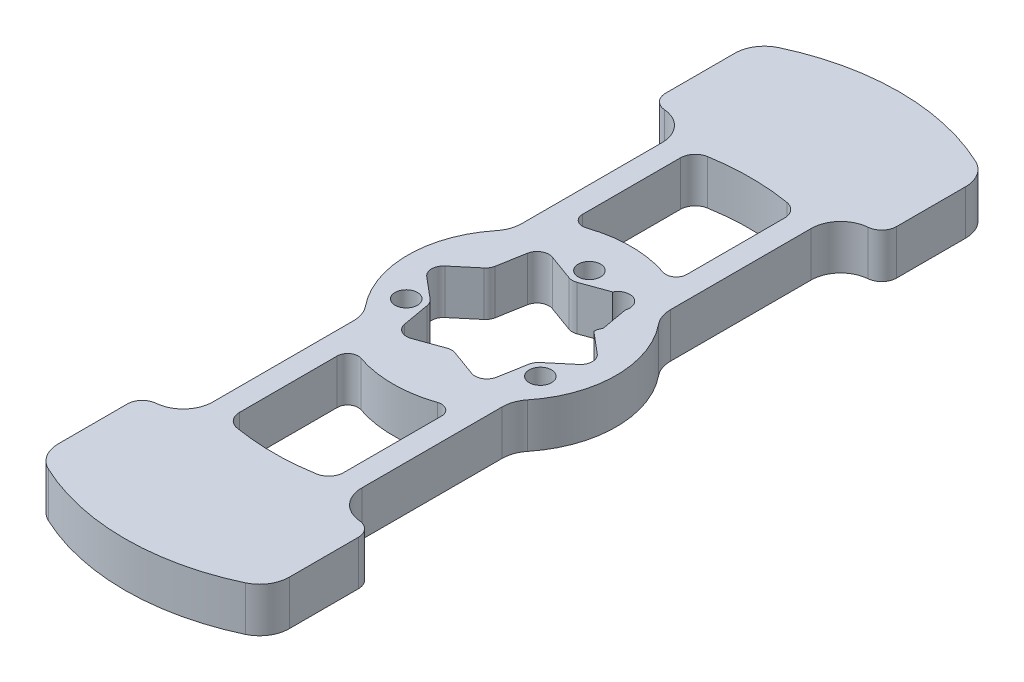
SolidWorks part; units mm, degrees
material "AISI 4340 Steel, annealed"
ref_plane "Front Plane" through (0, 0, 0) normal (0, 0, 1) x (1, 0, 0)
ref_plane "Top Plane" through (0, 0, 0) normal (0, 1, 0) x (1, 0, 0)
ref_plane "Right Plane" through (0, 0, 0) normal (1, 0, 0) x (0, 0, -1)
sketch "Sketch1" plane through (0, 0, 0) normal (0, 1, 0) x (1, 0, 0)
  line L0 (0, 0) -> (-15.875, 0) construction
  line L2 (-15.875, 47.8891) -> (-15.875, 17.9605)
  line L4 (15.875, 47.8891) -> (15.875, 17.9605)
  line L5 (-15.875, 50.8) -> (15.875, -50.8) construction
  line L6 (-15.875, -50.8) -> (15.875, 50.8) construction
  line L7 (6.4359, 15.0359) -> (0.8729, 13.0168)
  line L8 (-0.8603, 13.0122) -> (-6.4359, 15.0359)
  line L9 (-9.8035, 13.0916) -> (-10.8376, 7.2577)
  line L10 (-11.7042, 5.7568) -> (-16.2394, 1.9443)
  line L11 (-16.2394, -1.9443) -> (-11.7042, -5.7568)
  line L12 (-10.8376, -7.2577) -> (-9.8035, -13.0916)
  line L13 (-6.4359, -15.0359) -> (-0.8597, -13.012)
  line L14 (0.8724, -13.0166) -> (6.4359, -15.0359)
  line L15 (9.8035, -13.0916) -> (10.8376, -7.2577)
  line L16 (11.7042, -5.7568) -> (16.2394, -1.9443)
  line L17 (16.2394, 1.9443) -> (11.7042, 5.7568)
  line L18 (12.1466, 7.2577) -> (11.1125, 13.0916)
  line L19 (0.0067, 12.8621) -> (0.0067, -12.8621) construction
  line L20 (-17.145, 0) -> (12.065, 0) construction
  line L21 (15.875, -17.9605) -> (15.875, -47.8891)
  line L22 (-15.875, -17.9605) -> (-15.875, -47.8891)
  line L23 (-24.6267, -57.3827) -> (-24.6267, -72.1155)
  line L25 (24.6267, -57.3827) -> (24.6267, -72.1155)
  line L27 (-24.6267, 57.3827) -> (-24.6267, 72.1155)
  line L28 (24.6267, 57.3827) -> (24.6267, 72.1155)
  line L29 (-15.875, 41.3545) -> (-11.1125, 41.3545) construction
  line L30 (15.875, 36.8989) -> (11.1125, 36.8989) construction
  line L31 (-11.1125, 26.1528) -> (-11.1125, 47.0191)
  line L32 (11.1125, 47.0191) -> (11.1125, 26.1528)
  line L33 (-22.225, 0) -> (75.6572, 0) construction
  line L34 (11.1125, -47.0191) -> (11.1125, -26.1528)
  line L35 (-11.1125, -26.1528) -> (-11.1125, -47.0191)
  arc A2 (20.9799, 77.8614) -> (-20.9799, 77.8614) centre (0, 33.2669) ccw
  arc A3 (20.9799, -77.8614) -> (-20.9799, -77.8614) centre (0, -33.2669) cw
  arc A7 (-15.875, 47.8891) -> (-21.7095, 54.2182) centre (-22.225, 47.8891) ccw
  arc A8 (15.875, 47.8891) -> (21.7095, 54.2182) centre (22.225, 47.8891) cw
  arc A9 (-21.7095, -54.2182) -> (-15.875, -47.8891) centre (-22.225, -47.8891) ccw
  arc A10 (21.7095, -54.2182) -> (15.875, -47.8891) centre (22.225, -47.8891) cw
  circle A11 centre (-14.2981, -8.255) radius 2.3813
  circle A12 centre (0, 16.51) radius 2.3813
  circle A13 centre (14.2981, -8.255) radius 2.3813
  arc A14 (11.1125, 13.0916) -> (6.4359, 15.0359) centre (8.6984, 13.8815) ccw
  arc A15 (-0.8603, 13.0122) -> (0.8729, 13.0168) centre (0, 15.4021) ccw
  arc A16 (-6.4359, 15.0359) -> (-9.8035, 13.0916) centre (-7.3025, 12.6483) ccw
  arc A17 (-11.7042, 5.7568) -> (-10.8376, 7.2577) centre (-13.3386, 7.7011) ccw
  arc A18 (-16.2394, 1.9443) -> (-16.2394, -1.9443) centre (-14.605, 0) ccw
  arc A19 (-10.8376, -7.2577) -> (-11.7042, -5.7568) centre (-13.3386, -7.7011) ccw
  arc A20 (-9.8035, -13.0916) -> (-6.4359, -15.0359) centre (-7.3025, -12.6483) ccw
  arc A21 (0.8724, -13.0166) -> (-0.8597, -13.012) centre (0, -15.4021) ccw
  arc A22 (6.4359, -15.0359) -> (9.8035, -13.0916) centre (7.3025, -12.6483) ccw
  arc A23 (11.7042, -5.7568) -> (10.8376, -7.2577) centre (13.3386, -7.7011) ccw
  arc A24 (16.2394, -1.9443) -> (16.2394, 1.9443) centre (14.605, 0) ccw
  arc A25 (12.1466, 7.2577) -> (11.7042, 5.7568) centre (14.2433, 5.824) ccw
  arc A26 (-17.2861, 13.9693) -> (-17.2861, -13.9693) centre (0, 0) ccw
  arc A27 (17.2861, -13.9693) -> (17.2861, 13.9693) centre (0, 0) ccw
  arc A28 (-17.2861, 13.9693) -> (-15.875, 17.9605) centre (-22.225, 17.9605) ccw
  arc A29 (-15.875, -17.9605) -> (-17.2861, -13.9693) centre (-22.225, -17.9605) ccw
  arc A30 (15.875, -17.9605) -> (17.2861, -13.9693) centre (22.225, -17.9605) cw
  arc A31 (15.875, 17.9605) -> (17.2861, 13.9693) centre (22.225, 17.9605) ccw
  arc A36 (-24.6267, 72.1155) -> (-20.9799, 77.8614) centre (-18.2767, 72.1155) cw
  arc A37 (24.6267, 72.1155) -> (20.9799, 77.8614) centre (18.2767, 72.1155) ccw
  arc A38 (-24.6267, -72.1155) -> (-20.9799, -77.8614) centre (-18.2767, -72.1155) ccw
  arc A39 (20.9799, -77.8614) -> (24.6267, -72.1155) centre (18.2767, -72.1155) ccw
  arc A40 (-21.7095, -54.2182) -> (-24.6267, -57.3827) centre (-21.4517, -57.3827) ccw
  arc A41 (24.6267, -57.3827) -> (21.7095, -54.2182) centre (21.4517, -57.3827) ccw
  arc A42 (-21.7095, 54.2182) -> (-24.6267, 57.3827) centre (-21.4517, 57.3827) cw
  arc A43 (21.7095, 54.2182) -> (24.6267, 57.3827) centre (21.4517, 57.3827) ccw
  arc A44 (8.1747, 24.0486) -> (-8.1747, 24.0486) centre (0, 0) ccw construction
  arc A46 (-8.466, 50.1498) -> (8.466, 50.1498) centre (0, 0) cw
  arc A47 (-8.1747, 24.0486) -> (8.1747, 24.0486) centre (0, 0) cw
  arc A49 (8.466, 50.1498) -> (-8.466, 50.1498) centre (0, 0) ccw construction
  arc A50 (-11.1125, 47.0191) -> (-8.466, 50.1498) centre (-7.9375, 47.0191) cw
  arc A51 (11.1125, 47.0191) -> (8.466, 50.1498) centre (7.9375, 47.0191) ccw
  arc A52 (-11.1125, 26.1528) -> (-8.1747, 24.0486) centre (-8.89, 26.1528) ccw
  arc A53 (8.1747, 24.0486) -> (11.1125, 26.1528) centre (8.89, 26.1528) ccw
  arc A54 (8.1747, -24.0486) -> (11.1125, -26.1528) centre (8.89, -26.1528) cw
  arc A55 (-8.1747, -24.0486) -> (8.1747, -24.0486) centre (0, 0) ccw
  arc A56 (-11.1125, -26.1528) -> (-8.1747, -24.0486) centre (-8.89, -26.1528) cw
  arc A57 (-11.1125, -47.0191) -> (-8.466, -50.1498) centre (-7.9375, -47.0191) ccw
  arc A58 (-8.466, -50.1498) -> (8.466, -50.1498) centre (0, 0) ccw
  arc A59 (11.1125, -47.0191) -> (8.466, -50.1498) centre (7.9375, -47.0191) cw
  point P0 (0, 0)
  point P22 (-15.875, 56.6393)
  point P27 (-15.875, -56.6393)
  point P86 (15.875, -15.5543)
  point P91 (-49.1991, 36.1422)
  point P94 (49.1991, 36.1422)
  point P97 (-49.1991, -36.1422)
  point P100 (49.1991, -36.1422)
  dimension "D3" = 6.35
  dimension "D4" = 6.35
  dimension "D5" = 6.35
  dimension "D6" = 6.35
  dimension "D7" = 44.45
  dimension "D8" = 6.35
  dimension "D9" = 6.35
  dimension "D10" = 6.35
  dimension "D11" = 6.35
  dimension "D12" = 6.35
  dimension "D13" = 6.35
  dimension "D14" = 6.35
  dimension "D15" = 6.35
  dimension "D16" = 3.175
  dimension "D17" = 3.175
  dimension "D18" = 3.175
  dimension "D19" = 3.175
  dimension "D20" = 50.8
  dimension "D23" = 3.175
  dimension "D24" = 3.175
  dimension "D25" = 2.2225
  dimension "D26" = 2.2225
  dimension "D1" = 101.6
  dimension "D2" = 31.75
  dimension "D21" = 4.7625
  dimension "D22" = 4.7625
extrude "Boss-Extrude1" add sketch "Sketch1" along normal blind 9.525
